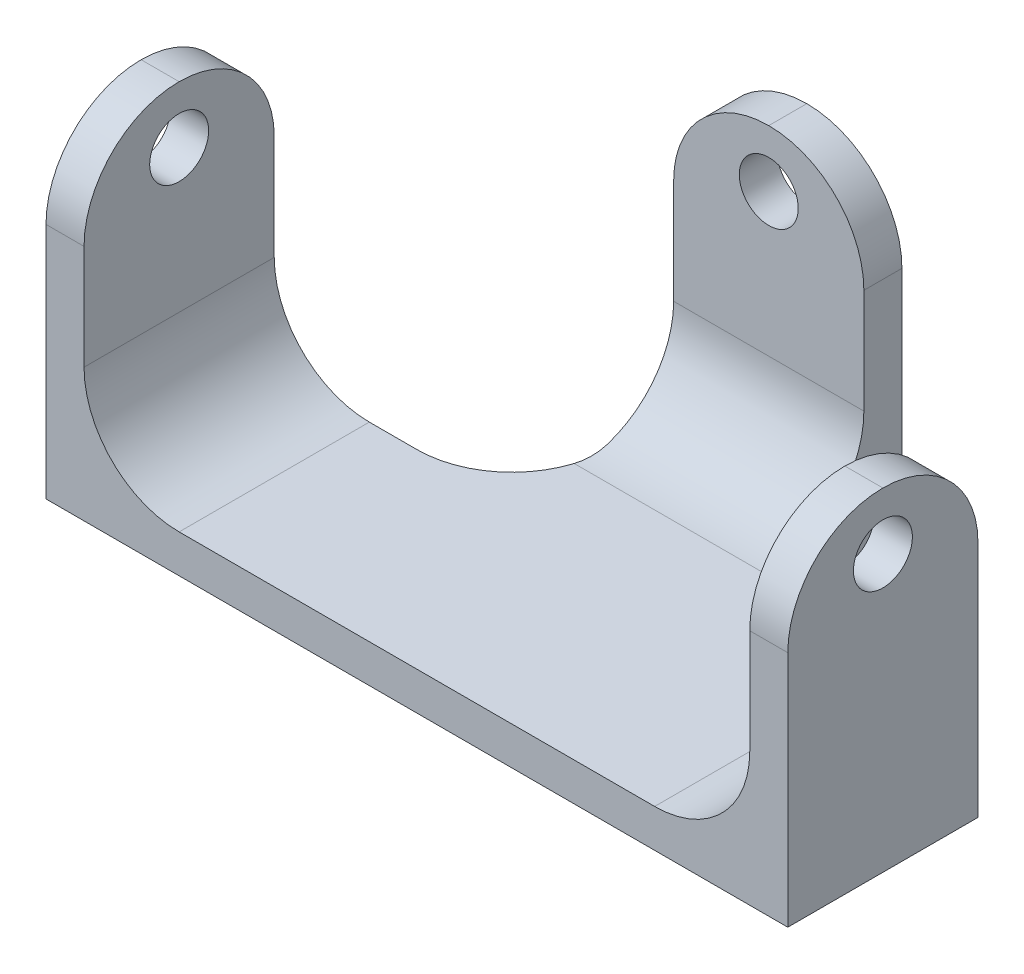
SolidWorks part; units mm, degrees
ref_plane "Front Plane" through (0, 0, 0) normal (0, 0, 1) x (1, 0, 0)
ref_plane "Top Plane" through (0, 0, 0) normal (0, 1, 0) x (1, 0, 0)
ref_plane "Right Plane" through (0, 0, 0) normal (1, 0, 0) x (0, 0, -1)
sketch "Sketch1" plane through (0, 0, 0) normal (0, 0, 1) x (1, 0, 0)
  line L0 (-10.6394, 6.8175) -> (-6.6394, 6.8175)
  line L1 (-6.6394, 6.8175) -> (-6.6394, -24.1825)
  line L2 (-6.6394, -24.1825) -> (63.3606, -24.1825)
  line L3 (63.3606, -24.1825) -> (63.3606, 6.8175)
  line L4 (63.3606, 6.8175) -> (67.3606, 6.8175)
  line L5 (67.3606, 6.8175) -> (67.3606, -28.1825)
  line L6 (67.3606, -28.1825) -> (-10.6394, -28.1825)
  line L7 (-10.6394, -28.1825) -> (-10.6394, 6.8175)
  dimension "D1" = 4
  dimension "D2" = 35
  dimension "D3" = 4
  dimension "D4" = 70
extrude "Boss-Extrude1" add sketch "Sketch1" along normal blind 62
sketch "Sketch2" plane through (0, -24.1825, 0) normal (0, 1, 0) x (1, 0, 0)
  line L0 (63.3606, 0) -> (-6.6394, 0) construction
  line L1 (-2.6394, 0) -> (59.3606, 0)
  line L2 (-2.6394, 0) -> (-2.6394, -4)
  line L3 (-2.6394, -4) -> (59.3606, -4)
  line L4 (59.3606, 0) -> (59.3606, -4)
  point P6 (28.3606, 0)
  point P9 (28.3606, 0)
  dimension "D1" = 4
  dimension "D2" = 62
extrude "Boss-Extrude2" add sketch "Sketch2" along normal blind 31
sketch "Sketch4" plane through (-6.6394, 0, 0) normal (1, 0, 0) x (0, 0, -1)
  line L0 (-62, 6.8175) -> (0, 6.8175) construction
  circle A0 centre (-31, 0.8175) radius 3.1
  point P2 (-31, 6.8175)
  dimension "D1" = 6.2
  dimension "D2" = 6
extrude "Cut-Extrude1" cut sketch "Sketch4" against normal through all both and the other way through all
sketch "Sketch5" plane through (0, 0, 4) normal (0, 0, 1) x (1, 0, 0)
  line L0 (-2.6394, 6.8175) -> (59.3606, 6.8175) construction
  circle A0 centre (28.3606, 0.8175) radius 3.1
  point P2 (28.3606, 6.8175)
  dimension "D2" = 6.2
  dimension "D1" = 6
extrude "Cut-Extrude2" cut sketch "Sketch5" against normal through all
sketch "Sketch6" plane through (0, -28.1825, 0) normal (0, -1, 0) x (1, 0, 0)
  line L0 (67.3606, 62) -> (67.3606, 0) construction
  line L2 (-10.6394, 62) -> (67.3606, 62)
  line L3 (-10.6394, 62) -> (-10.6394, 41)
  line L4 (-10.6394, 41) -> (67.3606, 41)
  line L5 (67.3606, 62) -> (67.3606, 41)
  line L6 (18.3606, 21) -> (38.3606, 21) construction
  line L7 (-10.6394, 0) -> (18.3606, 0)
  line L8 (-10.6394, 0) -> (-10.6394, 21)
  line L9 (-10.6394, 21) -> (18.3606, 21)
  line L10 (18.3606, 0) -> (18.3606, 21)
  line L11 (67.3606, 0) -> (38.3606, 0)
  line L12 (67.3606, 0) -> (67.3606, 21)
  line L13 (67.3606, 21) -> (38.3606, 21)
  line L14 (38.3606, 0) -> (38.3606, 21)
  line L15 (18.3606, 21) -> (18.3606, 41) construction
  dimension "D1" = 20
extrude "Cut-Extrude3" cut sketch "Sketch6" against normal through all
fillet "Fillet1" radius 10 9 edges at (65.3606, 6.8175, 41) (65.3606, 6.8175, 21) (-8.6394, 6.8175, 21) (-8.6394, 6.8175, 41) (38.3606, 6.8175, 2) (18.3606, 6.8175, 2) (-6.6394, -24.1825, 31) (28.3606, -24.1825, 4) (63.3606, -24.1825, 31)
fillet "Fillet2" radius 10 2 edges at (18.3606, -26.1825, 21) (38.3606, -26.1825, 21)
equation "\"standWidth\"= 62"
equation "\"D1@Boss-Extrude1\"=\"standWidth\""
equation "\"standThickness\"=4"
equation "\"D1@Sketch1\"=\"standThickness\""
equation "\"standHeight\"= 35"
equation "\"D2@Sketch2\"=\"standWidth\""
equation "\"D1@Sketch2\"=\"standThickness\""
equation "\"D1@Boss-Extrude2\"=\"standHeight\"-\"standThickness\""
equation "\"holeFromTop\"=6"
equation "\"D2@Sketch4\"=\"holeFromTop\""
equation "\"D1@Sketch5\"=\"holeFromTop\""
equation "\"D2@Sketch1\"=\"standHeight\""
